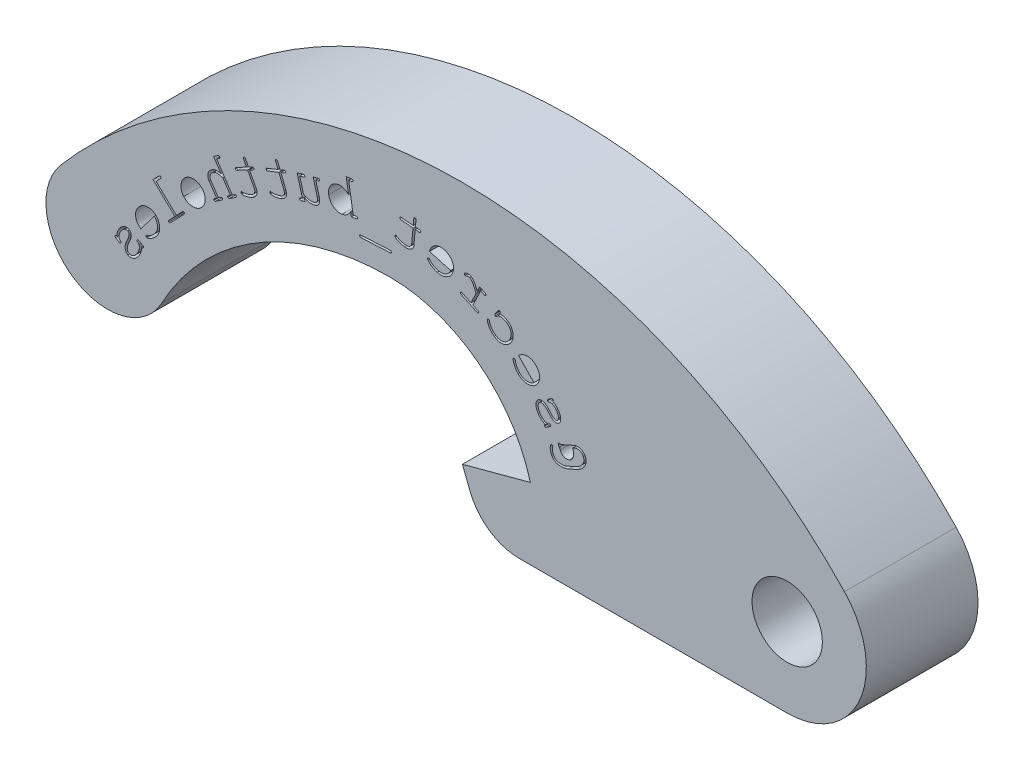
SolidWorks part; units mm, degrees
ref_plane "Front Plane" through (0, 0, 0) normal (0, 0, 1) x (1, 0, 0)
ref_plane "Top Plane" through (0, 0, 0) normal (0, 1, 0) x (1, 0, 0)
ref_plane "Right Plane" through (0, 0, 0) normal (1, 0, 0) x (0, 0, -1)
sketch "Model" plane through (0, 0, 0) normal (0, 0, 1) x (1, 0, 0)
  line L0 (118.4339, 164.6403) -> (103.198, 164.6403)
  line L1 (99.9692, 167.6594) -> (103.8317, 168.6993)
  line L2 (100.4041, 166.5474) -> (99.9692, 167.6594)
  arc A0 (103.8317, 168.6993) -> (95.8441, 174.8171) centre (95.8489, 166.5501) ccw
  arc A1 (95.8441, 174.8171) -> (82.8776, 167.0489) centre (95.8526, 160.0971) ccw
  arc A2 (77.1258, 170.9687) -> (82.8776, 167.0489) centre (79.7925, 168.7018) ccw
  arc A3 (121.6899, 172.2465) -> (77.1258, 170.9687) centre (99.9833, 151.5384) ccw
  arc A4 (118.4339, 164.6403) -> (121.6899, 172.2465) centre (118.4339, 169.1403) ccw
  circle A5 centre (118.4339, 169.1403) radius 2
  arc A6 (100.4041, 166.5474) -> (103.198, 164.6403) centre (103.198, 167.6403) ccw
  dimension "D1" = 4
  dimension "D2" = 8.267
  dimension "D3" = 14.72
  dimension "D4" = 3.5
  dimension "D5" = 30
  dimension "D6" = 4.5
  dimension "D7" = 3
  dimension "D8" = 77.1258
  dimension "D9" = 79.7925
  dimension "D10" = 82.8776
  dimension "D11" = 95.8441
  dimension "D12" = 99.9692
  dimension "D13" = 100.4041
  dimension "D14" = 103.198
  dimension "D15" = 103.8317
  dimension "D16" = 151.5384
extrude "Boss-Extrude1" add sketch "Model" along normal blind 6.35
sketch "Sketch1" plane through (0, 0, 0) normal (0, 0, -1) x (-1, 0, 0)
  arc A3 (-80.0287, 168.501) -> (-118.9332, 169.6165) centre (-99.9833, 151.5384) ccw
  arc A4 (-80.0287, 168.501) -> (-118.9332, 169.6165) centre (-99.9833, 151.5384) ccw construction
  text T0 "@secret_buttholes" font "Courier New" height in points 8
  dimension "D1" = 3.81
extrude "Cut-Extrude3" [suppressed] cut sketch "Sketch1" against normal through all from surface starting at face at (100.3432, 169.5142, 0)
sketch "Sketch6" plane through (0, 0, 0) normal (0, 0, -1) x (-1, 0, 0)
  arc A4 (-95.8425, 177.6111) -> (-106.5296, 169.4256) centre (-95.8489, 166.5501) ccw
  arc A5 (-80.4148, 168.3684) -> (-95.8425, 177.6111) centre (-95.8526, 160.0971) ccw
  arc A6 (-95.8425, 177.6111) -> (-106.5296, 169.4256) centre (-95.8489, 166.5501) ccw construction
  arc A7 (-80.4148, 168.3684) -> (-95.8425, 177.6111) centre (-95.8526, 160.0971) ccw construction
  spline S0 degree 1 poles (-106.5296, 169.4256) (-107.8032, 165.1957) knots 0 0 1 1 construction
  text T0 "@secret_buttholes" font "Courier New" height in points 10
  point P1 (-107.8032, 165.1957)
  dimension "D1" = 2.794
extrude "Cut-Extrude6" [suppressed] cut sketch "Sketch6" against normal through all
sketch "Sketch2" plane through (0, 0, 0) normal (0, 0, -1) x (-1, 0, 0)
  arc A4 (-81.0865, 168.0085) -> (-95.843, 176.8491) centre (-95.8526, 160.0971) ccw
  arc A5 (-95.843, 176.8491) -> (-105.7938, 169.2275) centre (-95.8489, 166.5501) ccw
  arc A6 (-81.0865, 168.0085) -> (-95.843, 176.8491) centre (-95.8526, 160.0971) ccw construction
  arc A7 (-95.843, 176.8491) -> (-105.7938, 169.2275) centre (-95.8489, 166.5501) ccw construction
  text T0 "@secret_buttholes" font "Courier New" height in points 8
  dimension "D2" = 77.1258
  dimension "D3" = 164.6403
  dimension "D1" = 2.032
extrude "Cut-Extrude4" cut sketch "Sketch2" against normal through all
sketch "Sketch4" plane through (0, 0, 0) normal (0, 0, -1) x (-1, 0, 0)
  line L0 (-82.3523, 171.1894) -> (-81.6602, 170.2872) construction
  line L1 (-105.6025, 171.3094) -> (-106.1203, 171.5408) construction
  line L2 (-104.1263, 173.8016) -> (-103.3383, 174.6092) construction
  line L3 (-99.3387, 176.9892) -> (-98.2482, 177.2891) construction
  line L4 (-82.3523, 171.1894) -> (-81.6602, 170.2872)
  line L5 (-105.6025, 171.3094) -> (-106.1203, 171.5408)
  line L6 (-104.1263, 173.8016) -> (-103.3383, 174.6092)
  line L7 (-99.3387, 176.9892) -> (-98.2482, 177.2891)
  spline S0 degree 3 poles (692.8817, -462.2332) (-91.6039, 173.8769) (-82.6238, 168.8978) (-81.5978, 170.3667) (-81.5735, 170.4096) (-81.5527, 170.4536) (-81.5367, 170.4993) (-81.5243, 170.5461) (-81.5164, 170.5948) (-81.5132, 170.6445) (-81.5134, 170.6946) (-81.5182, 170.7442) (-81.5274, 170.7928) (-81.5411, 170.8403) (-81.5589, 170.8869) (-81.5814, 170.9325) (-82.5552, 172.5727) (-91.7909, 168.6006) (743.3791, 736.1235) knots -6.526806 -6.526806 -6.526806 -6.526806 0.064285 0.126965 0.188563 0.249357 0.309597 0.369956 0.431324 0.494234 0.556995 0.619497 0.681148 0.742466 0.804999 0.868212 0.933071 7.959342 7.959342 7.959342 7.959342 only from (-81.6602, 170.2872) to (-81.6393, 171.0198) construction
  spline S1 degree 3 poles (679.8519, 819.1905) (-86.3746, 161.9667) (-80.3532, 169.6973) (-81.7086, 171.0984) (-81.7467, 171.1318) (-81.7869, 171.1611) (-81.8291, 171.1865) (-81.8731, 171.2085) (-81.9195, 171.2258) (-81.9673, 171.2392) (-82.0159, 171.249) (-82.0649, 171.2537) (-82.1136, 171.2542) (-82.162, 171.2502) (-82.2101, 171.2419) (-82.258, 171.2292) (-84.0463, 170.5726) (-81.8966, 160.9785) (-489.1104, 1084.7069) knots -7.114429 -7.114429 -7.114429 -7.114429 0.06664 0.131847 0.194872 0.256964 0.318156 0.379641 0.441453 0.503803 0.566075 0.627473 0.688034 0.748791 0.809693 0.871229 0.934574 7.951186 7.951186 7.951186 7.951186 only from (-81.6393, 171.0198) to (-82.3523, 171.1894) construction
  spline S2 degree 3 poles (-684.2365, -627.6416) (-82.0079, 183.438) (-86.5996, 173.9382) (-84.928, 172.8768) (-84.8783, 172.8524) (-84.8273, 172.8325) (-84.7743, 172.8185) (-84.7198, 172.8105) (-84.6638, 172.8067) (-84.6067, 172.8091) (-84.5501, 172.8164) (-84.4954, 172.8286) (-84.4432, 172.8455) (-84.3938, 172.868) (-84.3469, 172.895) (-84.3029, 172.9273) (-82.8906, 174.1821) (-89.2379, 182.9908) (634.9712, -521.7751) knots -6.474254 -6.474254 -6.474254 -6.474254 0.065392 0.128626 0.190445 0.251891 0.313241 0.374732 0.437597 0.502346 0.567097 0.629888 0.691271 0.752041 0.812658 0.873347 0.935832 7.17312 7.17312 7.17312 7.17312 only from (-85.0209, 172.9429) to (-84.2237, 173.0065) construction
  spline S3 degree 3 poles (719.087, -422.5521) (-94.9735, 176.4218) (-85.1447, 171.508) (-84.1586, 173.0984) (-84.1346, 173.1477) (-84.1149, 173.1983) (-84.1023, 173.251) (-84.0935, 173.305) (-84.0913, 173.3609) (-84.0938, 173.4177) (-84.1016, 173.474) (-84.1141, 173.5287) (-84.1323, 173.5807) (-84.1547, 173.6306) (-84.1831, 173.6775) (-84.2158, 173.7222) (-85.5177, 175.1607) (-94.2055, 168.8373) (602.199, 900.9224) knots -6.106401 -6.106401 -6.106401 -6.106401 0.0643 0.127258 0.188405 0.249203 0.309819 0.370811 0.433607 0.497871 0.562671 0.625078 0.686758 0.748162 0.809262 0.871305 0.934795 7.337401 7.337401 7.337401 7.337401 only from (-84.2237, 173.0065) to (-84.2969, 173.8024) construction
  spline S4 degree 3 poles (-279.7136, -1814.4995) (-96.1803, 192.8052) (-95.3271, 176.711) (-93.0074, 176.6684) (-92.9561, 176.6733) (-92.9057, 176.6834) (-92.8561, 176.6986) (-92.8077, 176.72) (-92.7598, 176.7456) (-92.7138, 176.777) (-92.67, 176.8117) (-92.6306, 176.8503) (-92.5959, 176.892) (-92.5658, 176.9367) (-92.5399, 176.9841) (-92.5194, 177.0349) (-91.8084, 179.3769) (-107.2217, 185.4776) (1856.3161, -272.0338) knots -7.872574 -7.872574 -7.872574 -7.872574 0.061522 0.121689 0.181097 0.240384 0.300187 0.361323 0.423981 0.489179 0.554629 0.618262 0.680724 0.742978 0.805636 0.86844 0.933373 9.306738 9.306738 9.306738 9.306738 only from (-93.1118, 176.6759) to (-92.4924, 177.1445)
  spline S5 degree 3 poles (1899.2355, -4.1363) (-109.4629, 173.9636) (-92.5296, 174.8626) (-92.4838, 177.2571) (-92.4875, 177.3119) (-92.4973, 177.365) (-92.5117, 177.417) (-92.5316, 177.4676) (-92.558, 177.5162) (-92.588, 177.5633) (-92.622, 177.6074) (-92.6594, 177.6467) (-92.6987, 177.6821) (-92.741, 177.7122) (-92.7859, 177.737) (-92.8329, 177.7579) (-94.9605, 178.4328) (-100.8826, 162.7581) (354.8184, 2126.9057) knots -8.119554 -8.119554 -8.119554 -8.119554 0.066632 0.131838 0.194665 0.257311 0.319229 0.382289 0.445813 0.511275 0.576472 0.63903 0.69988 0.760035 0.819082 0.878139 0.938552 8.561249 8.561249 8.561249 8.561249 only from (-92.4924, 177.1445) to (-92.9344, 177.7834)
  spline S6 degree 3 poles (2.3606, 1173.2297) (-90.2723, 167.5303) (-91.1868, 177.757) (-93.0388, 177.7909) (-93.0901, 177.786) (-93.1405, 177.7759) (-93.1901, 177.7607) (-93.2384, 177.7394) (-93.2864, 177.7137) (-93.3323, 177.6825) (-93.3758, 177.6475) (-93.4151, 177.6089) (-93.4503, 177.5677) (-93.4799, 177.5225) (-93.5061, 177.4752) (-93.5262, 177.4242) (-94.091, 175.6026) (-84.0783, 171.2606) (-1067.1979, 405.3446) knots -6.247903 -6.247903 -6.247903 -6.247903 0.061514 0.121673 0.181074 0.240354 0.300149 0.361277 0.423926 0.489116 0.554165 0.617789 0.680567 0.742532 0.805182 0.868446 0.932887 7.4296 7.4296 7.4296 7.4296 only from (-92.9344, 177.7834) to (-93.5533, 177.3145)
  spline S7 degree 3 poles (-2085.5705, 355.4969) (-76.537, 180.5043) (-93.517, 179.5899) (-93.5619, 177.2019) (-93.5584, 177.1473) (-93.5483, 177.0941) (-93.5343, 177.0421) (-93.5139, 176.9918) (-93.4883, 176.943) (-93.4581, 176.8961) (-93.4242, 176.8519) (-93.3867, 176.8127) (-93.3477, 176.7772) (-93.3049, 176.7478) (-93.2605, 176.7222) (-93.2133, 176.7015) (-91.0943, 176.0268) (-85.1124, 191.7486) (-547.3375, -1770.9527) knots -8.103745 -8.103745 -8.103745 -8.103745 0.066683 0.131433 0.194812 0.257008 0.31946 0.382098 0.445435 0.510947 0.576193 0.638798 0.699695 0.759604 0.818944 0.878047 0.938505 8.540395 8.540395 8.540395 8.540395 only from (-93.5533, 177.3145) to (-93.1118, 176.6759)
  spline S8 degree 3 poles (-93.1118, 176.6759) (-93.0942, 176.6737) (-93.0595, 176.6694) (-93.0074, 176.6684) (-92.9561, 176.6733) (-92.9057, 176.6834) (-92.8561, 176.6986) (-92.8077, 176.72) (-92.7598, 176.7456) (-92.7138, 176.777) (-92.67, 176.8117) (-92.6306, 176.8503) (-92.5959, 176.892) (-92.5658, 176.9367) (-92.5399, 176.9841) (-92.5194, 177.0349) (-92.5031, 177.0885) (-92.496, 177.1257) (-92.4924, 177.1445) knots 0 0 0 0 0.061522 0.121689 0.181097 0.240384 0.300187 0.361323 0.423981 0.489179 0.554629 0.618262 0.680724 0.742978 0.805636 0.86844 0.933373 1 1 1 1
  spline S9 degree 3 poles (-92.4924, 177.1445) (-92.4899, 177.1635) (-92.4849, 177.2011) (-92.4838, 177.2571) (-92.4875, 177.3119) (-92.4973, 177.365) (-92.5117, 177.417) (-92.5316, 177.4676) (-92.558, 177.5162) (-92.588, 177.5633) (-92.622, 177.6074) (-92.6594, 177.6467) (-92.6987, 177.6821) (-92.741, 177.7122) (-92.7859, 177.737) (-92.8329, 177.7579) (-92.8826, 177.7736) (-92.917, 177.7801) (-92.9344, 177.7834) knots 0 0 0 0 0.066632 0.131838 0.194665 0.257311 0.319229 0.382289 0.445813 0.511275 0.576472 0.63903 0.69988 0.760035 0.819082 0.878139 0.938552 1 1 1 1
  spline S10 degree 3 poles (-92.9344, 177.7834) (-92.9519, 177.7856) (-92.9867, 177.79) (-93.0388, 177.7909) (-93.0901, 177.786) (-93.1405, 177.7759) (-93.1901, 177.7607) (-93.2384, 177.7394) (-93.2864, 177.7137) (-93.3323, 177.6825) (-93.3758, 177.6475) (-93.4151, 177.6089) (-93.4503, 177.5677) (-93.4799, 177.5225) (-93.5061, 177.4752) (-93.5262, 177.4242) (-93.5428, 177.3706) (-93.5497, 177.3334) (-93.5533, 177.3145) knots 0 0 0 0 0.061514 0.121673 0.181074 0.240354 0.300149 0.361277 0.423926 0.489116 0.554165 0.617789 0.680567 0.742532 0.805182 0.868446 0.932887 1 1 1 1
  spline S11 degree 3 poles (-93.5533, 177.3145) (-93.5558, 177.2955) (-93.5609, 177.258) (-93.5619, 177.2019) (-93.5584, 177.1473) (-93.5483, 177.0941) (-93.5343, 177.0421) (-93.5139, 176.9918) (-93.4883, 176.943) (-93.4581, 176.8961) (-93.4242, 176.8519) (-93.3867, 176.8127) (-93.3477, 176.7772) (-93.3049, 176.7478) (-93.2605, 176.7222) (-93.2133, 176.7015) (-93.1636, 176.6857) (-93.1292, 176.6792) (-93.1118, 176.6759) knots 0 0 0 0 0.066683 0.131433 0.194812 0.257008 0.31946 0.382098 0.445435 0.510947 0.576193 0.638798 0.699695 0.759604 0.818944 0.878047 0.938505 1 1 1 1
  spline S12 degree 3 poles (509.781, 978.2071) (-87.3696, 163.1953) (-82.7351, 172.8252) (-84.3899, 173.8683) (-84.4393, 173.8933) (-84.4905, 173.9131) (-84.5436, 173.9272) (-84.5983, 173.9351) (-84.6544, 173.939) (-84.7114, 173.9364) (-84.7681, 173.9299) (-84.8228, 173.9174) (-84.8749, 173.9007) (-84.9241, 173.878) (-84.9709, 173.851) (-85.0152, 173.8191) (-86.4673, 172.5004) (-80.3908, 164.0024) (-811.5243, 860.9749) knots -6.394048 -6.394048 -6.394048 -6.394048 0.065377 0.128597 0.19062 0.252052 0.313389 0.37535 0.4382 0.502935 0.56761 0.630386 0.691756 0.752065 0.812669 0.87374 0.935847 7.413888 7.413888 7.413888 7.413888 only from (-84.2969, 173.8024) to (-85.0941, 173.7396) construction
  spline S13 degree 3 poles (-894.3348, 761.2115) (-74.2223, 170.2606) (-84.2059, 175.2074) (-85.1581, 173.6484) (-85.1826, 173.5997) (-85.2012, 173.5489) (-85.215, 173.4964) (-85.2225, 173.442) (-85.2259, 173.386) (-85.223, 173.3289) (-85.2153, 173.2723) (-85.2026, 173.2175) (-85.1854, 173.165) (-85.1624, 173.1153) (-85.1344, 173.0682) (-85.1013, 173.0236) (-83.9021, 171.6466) (-74.6981, 178.4357) (-782.3943, -543.7523) knots -5.96211 -5.96211 -5.96211 -5.96211 0.063621 0.125912 0.186627 0.247261 0.308006 0.369418 0.432246 0.497009 0.561817 0.624709 0.686705 0.747671 0.809199 0.871251 0.934787 6.954545 6.954545 6.954545 6.954545 only from (-85.0941, 173.7396) to (-85.0209, 172.9429) construction
  spline S14 degree 3 poles (-1037.054, 536.7271) (-96.4713, 171.6324) (-105.5836, 173.2007) (-106.1525, 171.4548) (-106.1626, 171.413) (-106.1687, 171.3723) (-106.1713, 171.333) (-106.1708, 171.2948) (-106.1653, 171.2579) (-106.1567, 171.2224) (-106.145, 171.1891) (-106.1309, 171.1583) (-106.1149, 171.1301) (-106.0961, 171.1049) (-106.0754, 171.0824) (-106.0525, 171.0626) (-105.0916, 170.4106) (-99.614, 177.9169) (-588.3346, -704.9489) knots -9.230272 -9.230272 -9.230272 -9.230272 0.081724 0.159015 0.233026 0.303536 0.371161 0.436405 0.500021 0.563301 0.624476 0.682181 0.737605 0.791736 0.843733 0.89529 0.947691 6.814939 6.814939 6.814939 6.814939 only from (-106.1203, 171.5408) to (-106, 171.0322) construction
  spline S15 degree 3 poles (-371.8808, -792.9721) (-104.917, 185.0648) (-107.2848, 171.1545) (-105.8979, 171.007) (-105.8458, 171.0113) (-105.7946, 171.0273) (-105.7457, 171.0544) (-105.7022, 171.0938) (-104.615, 172.5275) (-115.5886, 180.9704) (760.8519, -327.9738) knots -8.784312 -8.784312 -8.784312 -8.784312 0.118848 0.233062 0.344972 0.462633 0.584838 0.712153 0.848643 12.410586 12.410586 12.410586 12.410586 only from (-106, 171.0322) to (-105.6347, 171.2039) construction
  spline S16 degree 3 poles (835.4623, -166.9301) (-114.3269, 172.16) (-105.8924, 170.2499) (-105.6173, 171.2537) (-105.1991, 172.6353) (-111.6938, 175.9014) (859.9666, -88.8101) knots -27.486653 -27.486653 -27.486653 -27.486653 0.230084 0.473486 0.732026 39.438937 39.438937 39.438937 39.438937 only from (-105.6347, 171.2039) to (-105.6025, 171.3094) construction
  spline S17 degree 3 poles (420.5842, 1026.3734) (-105.0584, 164.7049) (-101.7403, 173.7843) (-103.4253, 174.6596) (-103.4707, 174.6772) (-103.5168, 174.6915) (-103.564, 174.701) (-103.6121, 174.7064) (-103.6611, 174.7065) (-103.7106, 174.7032) (-103.7596, 174.6954) (-103.8074, 174.6835) (-103.8537, 174.6679) (-103.8985, 174.6476) (-103.9416, 174.6232) (-103.9831, 174.5946) (-105.4156, 173.4585) (-99.8911, 164.6416) (-778.1193, 913.1904) knots -6.98011 -6.98011 -6.98011 -6.98011 0.06468 0.127129 0.188582 0.248924 0.309513 0.370341 0.431912 0.494735 0.557636 0.619367 0.680906 0.742416 0.804942 0.868219 0.933124 7.711464 7.711464 7.711464 7.711464 only from (-103.3383, 174.6092) to (-104.0609, 174.5255) construction
  spline S18 degree 3 poles (-858.2638, 831.1663) (-94.392, 171.1089) (-102.9565, 175.9708) (-104.1278, 174.4464) (-104.1556, 174.4045) (-104.1788, 174.3609) (-104.1974, 174.3156) (-104.2129, 174.2694) (-104.2238, 174.2215) (-104.2303, 174.1727) (-104.2323, 174.1235) (-104.231, 174.0749) (-104.224, 174.0272) (-104.2139, 173.98) (-104.1982, 173.9339) (-104.1786, 173.8888) (-103.3335, 172.2892) (-93.7594, 176.083) (-952.9092, -354.9346) knots -7.073147 -7.073147 -7.073147 -7.073147 0.066587 0.131267 0.194413 0.256653 0.318034 0.379422 0.440921 0.503609 0.565812 0.626894 0.687402 0.748243 0.80911 0.871427 0.93441 7.644252 7.644252 7.644252 7.644252 only from (-104.0609, 174.5255) to (-104.1263, 173.8016) construction
  spline S19 degree 3 poles (780.4963, 654.579) (-104.5657, 169.5951) (-97.277, 175.763) (-98.298, 177.3762) (-98.3281, 177.4148) (-98.3609, 177.4505) (-98.397, 177.4824) (-98.4357, 177.5112) (-98.4776, 177.5367) (-98.5221, 177.5587) (-98.5685, 177.5769) (-98.6159, 177.5911) (-98.6641, 177.6005) (-98.7131, 177.6059) (-98.7627, 177.6067) (-98.8131, 177.6031) (-100.6985, 177.3183) (-100.4909, 167.2976) (-312.8681, 1154.4081) knots -7.008368 -7.008368 -7.008368 -7.008368 0.064063 0.126467 0.188253 0.248818 0.309053 0.369844 0.430912 0.493971 0.557037 0.618838 0.680922 0.742177 0.804733 0.86798 0.932928 7.994008 7.994008 7.994008 7.994008 only from (-98.2482, 177.2891) to (-98.9155, 177.5824) construction
  spline S20 degree 3 poles (-408.8316, 1128.346) (-92.3423, 170.0433) (-97.1619, 178.2859) (-99.0139, 177.548) (-99.0588, 177.5252) (-99.1013, 177.4995) (-99.1402, 177.4696) (-99.1772, 177.4374) (-99.2109, 177.4014) (-99.2411, 177.3623) (-99.2683, 177.3211) (-99.2908, 177.2777) (-99.3098, 177.2332) (-99.3242, 177.1873) (-99.3342, 177.1398) (-99.3403, 177.091) (-99.4084, 175.2649) (-89.3385, 173.7465) (-1098.7496, 142.9605) knots -7.319675 -7.319675 -7.319675 -7.319675 0.066787 0.131772 0.195062 0.25687 0.318743 0.380148 0.441849 0.50439 0.566615 0.627954 0.688671 0.749044 0.809612 0.871525 0.934643 7.695418 7.695418 7.695418 7.695418 only from (-98.9155, 177.5824) to (-99.3387, 176.9892) construction
  spline S21 degree 3 poles (-81.6602, 170.2872) (-81.6489, 170.3) (-81.6266, 170.3255) (-81.5978, 170.3667) (-81.5735, 170.4096) (-81.5527, 170.4536) (-81.5367, 170.4993) (-81.5243, 170.5461) (-81.5164, 170.5948) (-81.5132, 170.6445) (-81.5134, 170.6946) (-81.5182, 170.7442) (-81.5274, 170.7928) (-81.5411, 170.8403) (-81.5589, 170.8869) (-81.5814, 170.9325) (-81.6079, 170.9772) (-81.6287, 171.0055) (-81.6393, 171.0198) knots 0 0 0 0 0.064285 0.126965 0.188563 0.249357 0.309597 0.369956 0.431324 0.494234 0.556995 0.619497 0.681148 0.742466 0.804999 0.868212 0.933071 1 1 1 1
  spline S22 degree 3 poles (-81.6393, 171.0198) (-81.6504, 171.0337) (-81.6724, 171.061) (-81.7086, 171.0984) (-81.7467, 171.1318) (-81.7869, 171.1611) (-81.8291, 171.1865) (-81.8731, 171.2085) (-81.9195, 171.2258) (-81.9673, 171.2392) (-82.0159, 171.249) (-82.0649, 171.2537) (-82.1136, 171.2542) (-82.162, 171.2502) (-82.2101, 171.2419) (-82.258, 171.2292) (-82.3057, 171.2117) (-82.3366, 171.1969) (-82.3523, 171.1894) knots 0 0 0 0 0.06664 0.131847 0.194872 0.256964 0.318156 0.379641 0.441453 0.503803 0.566075 0.627473 0.688034 0.748791 0.809693 0.871229 0.934574 1 1 1 1
  spline S23 degree 3 poles (-85.0209, 172.9429) (-85.0057, 172.9308) (-84.9758, 172.9071) (-84.928, 172.8768) (-84.8783, 172.8524) (-84.8273, 172.8325) (-84.7743, 172.8185) (-84.7198, 172.8105) (-84.6638, 172.8067) (-84.6067, 172.8091) (-84.5501, 172.8164) (-84.4954, 172.8286) (-84.4432, 172.8455) (-84.3938, 172.868) (-84.3469, 172.895) (-84.3029, 172.9273) (-84.2613, 172.9642) (-84.2364, 172.9923) (-84.2237, 173.0065) knots 0 0 0 0 0.065392 0.128626 0.190445 0.251891 0.313241 0.374732 0.437597 0.502346 0.567097 0.629888 0.691271 0.752041 0.812658 0.873347 0.935832 1 1 1 1
  spline S24 degree 3 poles (-84.2237, 173.0065) (-84.2118, 173.0214) (-84.1881, 173.0508) (-84.1586, 173.0984) (-84.1346, 173.1477) (-84.1149, 173.1983) (-84.1023, 173.251) (-84.0935, 173.305) (-84.0913, 173.3609) (-84.0938, 173.4177) (-84.1016, 173.474) (-84.1141, 173.5287) (-84.1323, 173.5807) (-84.1547, 173.6306) (-84.1831, 173.6775) (-84.2158, 173.7222) (-84.2538, 173.7643) (-84.2824, 173.7895) (-84.2969, 173.8024) knots 0 0 0 0 0.0643 0.127258 0.188405 0.249203 0.309819 0.370811 0.433607 0.497871 0.562671 0.625078 0.686758 0.748162 0.809262 0.871305 0.934795 1 1 1 1
  spline S25 degree 3 poles (-84.2969, 173.8024) (-84.3121, 173.8144) (-84.342, 173.8381) (-84.3899, 173.8683) (-84.4393, 173.8933) (-84.4905, 173.9131) (-84.5436, 173.9272) (-84.5983, 173.9351) (-84.6544, 173.939) (-84.7114, 173.9364) (-84.7681, 173.9299) (-84.8228, 173.9174) (-84.8749, 173.9007) (-84.9241, 173.878) (-84.9709, 173.851) (-85.0152, 173.8191) (-85.0564, 173.7817) (-85.0814, 173.7538) (-85.0941, 173.7396) knots 0 0 0 0 0.065377 0.128597 0.19062 0.252052 0.313389 0.37535 0.4382 0.502935 0.56761 0.630386 0.691756 0.752065 0.812669 0.87374 0.935847 1 1 1 1
  spline S26 degree 3 poles (-85.0941, 173.7396) (-85.1059, 173.7249) (-85.1292, 173.6957) (-85.1581, 173.6484) (-85.1826, 173.5997) (-85.2012, 173.5489) (-85.215, 173.4964) (-85.2225, 173.442) (-85.2259, 173.386) (-85.223, 173.3289) (-85.2153, 173.2723) (-85.2026, 173.2175) (-85.1854, 173.165) (-85.1624, 173.1153) (-85.1344, 173.0682) (-85.1013, 173.0236) (-85.0641, 172.9808) (-85.0354, 172.9556) (-85.0209, 172.9429) knots 0 0 0 0 0.063621 0.125912 0.186627 0.247261 0.308006 0.369418 0.432246 0.497009 0.561817 0.624709 0.686705 0.747671 0.809199 0.871251 0.934787 1 1 1 1
  spline S27 degree 3 poles (-106.1203, 171.5408) (-106.1264, 171.5262) (-106.1385, 171.4978) (-106.1525, 171.4548) (-106.1626, 171.413) (-106.1687, 171.3723) (-106.1713, 171.333) (-106.1708, 171.2948) (-106.1653, 171.2579) (-106.1567, 171.2224) (-106.145, 171.1891) (-106.1309, 171.1583) (-106.1149, 171.1301) (-106.0961, 171.1049) (-106.0754, 171.0824) (-106.0525, 171.0626) (-106.0274, 171.0455) (-106.0091, 171.0366) (-106, 171.0322) knots 0 0 0 0 0.081724 0.159015 0.233026 0.303536 0.371161 0.436405 0.500021 0.563301 0.624476 0.682181 0.737605 0.791736 0.843733 0.89529 0.947691 1 1 1 1
  spline S28 degree 3 poles (-106, 171.0322) (-105.9832, 171.0256) (-105.9503, 171.0126) (-105.8979, 171.007) (-105.8458, 171.0113) (-105.7946, 171.0273) (-105.7457, 171.0544) (-105.7022, 171.0938) (-105.664, 171.1442) (-105.6448, 171.1833) (-105.6347, 171.2039) knots 0 0 0 0 0.118848 0.233062 0.344972 0.462633 0.584838 0.712153 0.848643 1 1 1 1
  spline S29 degree 3 poles (-105.6347, 171.2039) (-105.6314, 171.2117) (-105.6244, 171.2277) (-105.6173, 171.2537) (-105.6091, 171.2809) (-105.6047, 171.2998) (-105.6025, 171.3094) knots 0 0 0 0 0.230084 0.473486 0.732026 1 1 1 1
  spline S30 degree 3 poles (-103.3383, 174.6092) (-103.3527, 174.6184) (-103.3809, 174.6366) (-103.4253, 174.6596) (-103.4707, 174.6772) (-103.5168, 174.6915) (-103.564, 174.701) (-103.6121, 174.7064) (-103.6611, 174.7065) (-103.7106, 174.7032) (-103.7596, 174.6954) (-103.8074, 174.6835) (-103.8537, 174.6679) (-103.8985, 174.6476) (-103.9416, 174.6232) (-103.9831, 174.5946) (-104.0236, 174.5625) (-104.0483, 174.538) (-104.0609, 174.5255) knots 0 0 0 0 0.06468 0.127129 0.188582 0.248924 0.309513 0.370341 0.431912 0.494735 0.557636 0.619367 0.680906 0.742416 0.804942 0.868219 0.933124 1 1 1 1
  spline S31 degree 3 poles (-104.0609, 174.5255) (-104.0729, 174.5126) (-104.0965, 174.4872) (-104.1278, 174.4464) (-104.1556, 174.4045) (-104.1788, 174.3609) (-104.1974, 174.3156) (-104.2129, 174.2694) (-104.2238, 174.2215) (-104.2303, 174.1727) (-104.2323, 174.1235) (-104.231, 174.0749) (-104.224, 174.0272) (-104.2139, 173.98) (-104.1982, 173.9339) (-104.1786, 173.8888) (-104.155, 173.8441) (-104.136, 173.8159) (-104.1263, 173.8016) knots 0 0 0 0 0.066587 0.131267 0.194413 0.256653 0.318034 0.379422 0.440921 0.503609 0.565812 0.626894 0.687402 0.748243 0.80911 0.871427 0.93441 1 1 1 1
  spline S32 degree 3 poles (-98.2482, 177.2891) (-98.256, 177.3042) (-98.2713, 177.334) (-98.298, 177.3762) (-98.3281, 177.4148) (-98.3609, 177.4505) (-98.397, 177.4824) (-98.4357, 177.5112) (-98.4776, 177.5367) (-98.5221, 177.5587) (-98.5685, 177.5769) (-98.6159, 177.5911) (-98.6641, 177.6005) (-98.7131, 177.6059) (-98.7627, 177.6067) (-98.8131, 177.6031) (-98.8644, 177.5954) (-98.8983, 177.5868) (-98.9155, 177.5824) knots 0 0 0 0 0.064063 0.126467 0.188253 0.248818 0.309053 0.369844 0.430912 0.493971 0.557037 0.618838 0.680922 0.742177 0.804733 0.86798 0.932928 1 1 1 1
  spline S33 degree 3 poles (-98.9155, 177.5824) (-98.9324, 177.5773) (-98.9658, 177.5672) (-99.0139, 177.548) (-99.0588, 177.5252) (-99.1013, 177.4995) (-99.1402, 177.4696) (-99.1772, 177.4374) (-99.2109, 177.4014) (-99.2411, 177.3623) (-99.2683, 177.3211) (-99.2908, 177.2777) (-99.3098, 177.2332) (-99.3242, 177.1873) (-99.3342, 177.1398) (-99.3403, 177.091) (-99.3422, 177.0405) (-99.3399, 177.0065) (-99.3387, 176.9892) knots 0 0 0 0 0.066787 0.131772 0.195062 0.25687 0.318743 0.380148 0.441849 0.50439 0.566615 0.627954 0.688671 0.749044 0.809612 0.871525 0.934643 1 1 1 1
  dimension "D1" = 0
extrude "Cut-Extrude5" cut sketch "Sketch4" against normal through all
